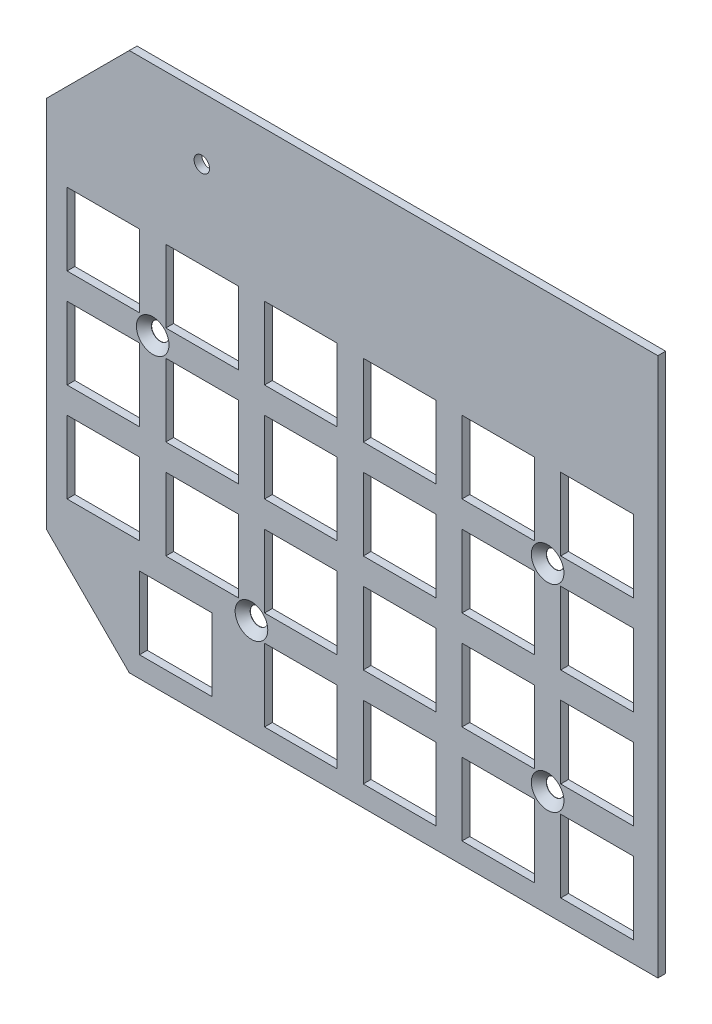
SolidWorks part; units mm, degrees
material "Alliage 1060"
ref_plane "Plan de face" through (0, 0, 0) normal (0, 0, 1) x (1, 0, 0)
ref_plane "Plan de dessus" through (0, 0, 0) normal (0, 1, 0) x (1, 0, 0)
ref_plane "Plan de droite" through (0, 0, 0) normal (1, 0, 0) x (0, 0, -1)
other "Centre de masse"
sketch "Esquisse1" plane through (0, 0, 0) normal (0, 0, 1) x (1, 0, 0)
  line L0 (0, -85) -> (16, -101)
  line L4 (118, 3) -> (118, -101)
  line L5 (16, 3) -> (0, -13)
  line L7 (118, 3) -> (16, 3)
  line L8 (0, -13) -> (0, -85)
  line L9 (16, -101) -> (118, -101)
  dimension "D1" = 104
  dimension "D2" = 118
  dimension "D3" = 16
  dimension "D4" = 16
  dimension "D5" = 16
  dimension "D6" = 16
extrude "Boss.-Extru.1" add sketch "Esquisse1" along normal blind 1.5
sketch "Esquisse2" plane through (0, 0, 1.5) normal (0, 0, 1) x (1, 0, 0)
  line L0 (0, -13) -> (0, -85) construction
  line L1 (4, -25.85) -> (18, -25.85)
  line L2 (4, -25.85) -> (4, -39.85)
  line L3 (4, -39.85) -> (18, -39.85)
  line L4 (18, -25.85) -> (18, -39.85)
  line L5 (11, -39.85) -> (11, -25.85) construction
  line L6 (4, -32.85) -> (18, -32.85) construction
  line L7 (118, 3) -> (16, 3) construction
  line L12 (23.05, -25.85) -> (23.05, -39.85)
  line L13 (23.05, -25.85) -> (37.05, -25.85)
  line L14 (37.05, -25.85) -> (37.05, -39.85)
  line L15 (23.05, -39.85) -> (37.05, -39.85)
  line L16 (42.1, -25.85) -> (42.1, -39.85)
  line L17 (42.1, -25.85) -> (56.1, -25.85)
  line L18 (56.1, -25.85) -> (56.1, -39.85)
  line L19 (42.1, -39.85) -> (56.1, -39.85)
  line L20 (61.15, -25.85) -> (61.15, -39.85)
  line L21 (61.15, -25.85) -> (75.15, -25.85)
  line L22 (75.15, -25.85) -> (75.15, -39.85)
  line L23 (61.15, -39.85) -> (75.15, -39.85)
  line L24 (80.2, -25.85) -> (80.2, -39.85)
  line L25 (80.2, -25.85) -> (94.2, -25.85)
  line L26 (94.2, -25.85) -> (94.2, -39.85)
  line L27 (80.2, -39.85) -> (94.2, -39.85)
  line L28 (99.25, -25.85) -> (99.25, -39.85)
  line L29 (99.25, -25.85) -> (113.25, -25.85)
  line L30 (113.25, -25.85) -> (113.25, -39.85)
  line L31 (99.25, -39.85) -> (113.25, -39.85)
  line L32 (23.05, -44.9) -> (23.05, -58.9)
  line L33 (23.05, -44.9) -> (37.05, -44.9)
  line L34 (37.05, -44.9) -> (37.05, -58.9)
  line L35 (23.05, -58.9) -> (37.05, -58.9)
  line L36 (42.1, -44.9) -> (42.1, -58.9)
  line L37 (42.1, -44.9) -> (56.1, -44.9)
  line L38 (56.1, -44.9) -> (56.1, -58.9)
  line L39 (42.1, -58.9) -> (56.1, -58.9)
  line L40 (61.15, -44.9) -> (61.15, -58.9)
  line L41 (61.15, -44.9) -> (75.15, -44.9)
  line L42 (75.15, -44.9) -> (75.15, -58.9)
  line L43 (61.15, -58.9) -> (75.15, -58.9)
  line L44 (80.2, -44.9) -> (80.2, -58.9)
  line L45 (80.2, -44.9) -> (94.2, -44.9)
  line L46 (94.2, -44.9) -> (94.2, -58.9)
  line L47 (80.2, -58.9) -> (94.2, -58.9)
  line L48 (99.25, -44.9) -> (99.25, -58.9)
  line L49 (99.25, -44.9) -> (113.25, -44.9)
  line L50 (113.25, -44.9) -> (113.25, -58.9)
  line L51 (99.25, -58.9) -> (113.25, -58.9)
  line L52 (23.05, -63.95) -> (23.05, -77.95)
  line L53 (23.05, -63.95) -> (37.05, -63.95)
  line L54 (37.05, -63.95) -> (37.05, -77.95)
  line L55 (23.05, -77.95) -> (37.05, -77.95)
  line L56 (42.1, -63.95) -> (42.1, -77.95)
  line L57 (42.1, -63.95) -> (56.1, -63.95)
  line L58 (56.1, -63.95) -> (56.1, -77.95)
  line L59 (42.1, -77.95) -> (56.1, -77.95)
  line L60 (61.15, -63.95) -> (61.15, -77.95)
  line L61 (61.15, -63.95) -> (75.15, -63.95)
  line L62 (75.15, -63.95) -> (75.15, -77.95)
  line L63 (61.15, -77.95) -> (75.15, -77.95)
  line L64 (80.2, -63.95) -> (80.2, -77.95)
  line L65 (80.2, -63.95) -> (94.2, -63.95)
  line L66 (94.2, -63.95) -> (94.2, -77.95)
  line L67 (80.2, -77.95) -> (94.2, -77.95)
  line L68 (99.25, -63.95) -> (99.25, -77.95)
  line L69 (99.25, -63.95) -> (113.25, -63.95)
  line L70 (113.25, -63.95) -> (113.25, -77.95)
  line L71 (99.25, -77.95) -> (113.25, -77.95)
  line L72 (4, -44.9) -> (4, -58.9)
  line L73 (4, -44.9) -> (18, -44.9)
  line L74 (18, -44.9) -> (18, -58.9)
  line L75 (4, -58.9) -> (18, -58.9)
  line L76 (4, -63.95) -> (4, -77.95)
  line L77 (4, -63.95) -> (18, -63.95)
  line L78 (18, -63.95) -> (18, -77.95)
  line L79 (4, -77.95) -> (18, -77.95)
  line L112 (42.1, -83) -> (42.1, -97)
  line L113 (42.1, -83) -> (56.1, -83)
  line L114 (56.1, -83) -> (56.1, -97)
  line L115 (42.1, -97) -> (56.1, -97)
  line L116 (61.15, -83) -> (61.15, -97)
  line L117 (61.15, -83) -> (75.15, -83)
  line L118 (75.15, -83) -> (75.15, -97)
  line L119 (61.15, -97) -> (75.15, -97)
  line L120 (80.2, -83) -> (80.2, -97)
  line L121 (80.2, -83) -> (94.2, -83)
  line L122 (94.2, -83) -> (94.2, -97)
  line L123 (80.2, -97) -> (94.2, -97)
  line L124 (99.25, -83) -> (99.25, -97)
  line L125 (99.25, -83) -> (113.25, -83)
  line L126 (113.25, -83) -> (113.25, -97)
  line L127 (99.25, -97) -> (113.25, -97)
  line L128 (4, -83) -> (4, -97) [skipped]
  line L129 (4, -83) -> (18, -83) [skipped]
  line L130 (18, -83) -> (18, -97) [skipped]
  line L131 (4, -97) -> (18, -97) [skipped]
  line L132 (23.05, -83) -> (23.05, -97) [skipped]
  line L133 (23.05, -83) -> (37.05, -83) [skipped]
  line L134 (37.05, -83) -> (37.05, -97) [skipped]
  line L135 (23.05, -97) -> (37.05, -97) [skipped]
  line L137 (17.97, -83) -> (31.97, -83)
  line L138 (17.97, -83) -> (17.97, -97)
  line L139 (17.97, -97) -> (31.97, -97)
  line L140 (31.97, -83) -> (31.97, -97)
  line L141 (24.97, -97) -> (24.97, -83) construction
  line L142 (17.97, -90) -> (31.97, -90) construction
  line L143 (16, -101) -> (118, -101) construction
  circle A8 centre (30, -9) radius 1.5
  point P0 (11, -32.85)
  point P19 (24.97, -90)
  dimension "D5" = 4
  dimension "D13" = 5.05
  dimension "D7" = 12
  dimension "D6" = 30
  dimension "D1" = 14
  dimension "D2" = 14
  dimension "D3" = 4
  dimension "D4" = 6
  dimension "D9" = 14
  dimension "D10" = 14
  dimension "D11" = 10.13
  dimension "D12" = 5.05
  dimension "D8" = 4
extrude "Enlèv. mat.-Extru.1" cut sketch "Esquisse2" against normal blind 1.5
sketch "Esquisse9" plane through (0, 0, 1.5) normal (0, 0, 1) x (1, 0, 0)
  line L0 (18, -44.9) -> (23.05, -39.85) construction
  line L1 (94.2, -39.85) -> (99.25, -44.9) construction
  line L2 (94.2, -83) -> (99.25, -77.95) construction
  line L3 (37.05, -77.95) -> (42.1, -83) construction
  point P16 (20.525, -42.375)
  point P17 (39.575, -80.475)
  point P18 (96.725, -42.375)
  point P19 (96.725, -80.475)
hole_wizard "Fraisage pour vis à tête fraisée M31" positions "Esquisse17" profile "Esquisse18" countersink size "M3" standard "Ansi Metric" end condition through all
sketch "Esquisse17" plane through (0, 0, 1.5) normal (0, 0, 1) x (1, 0, 0)
  point P0 (20.525, -42.375)
  point P4 (96.725, -42.375)
  point P7 (96.725, -80.475)
  point P10 (39.575, -80.475)
sketch "Esquisse18" plane through (20.525, -42.375, 1.5) normal (1, 0, 0) x (0, -1, 0)
  line L0 (0, 0) -> (0, 1.5)
  line L1 (0, 1.5) -> (1.7, 1.5)
  line L2 (1.7, 1.5) -> (1.7, 1.45)
  line L3 (1.7, 1.45) -> (3.15, 0)
  line L5 (3.15, 0) -> (0, 0)
  line L6 (-1.7, 1.45) -> (-3.15, 0) construction
  line L11 (0, -6.35) -> (0, 107.95) construction
  dimension "Diamètre du perçage jusqu'au prochain" = 3.4
  dimension "Profondeur du perçage jusqu'au prochain" = 1.5
  dimension "Diamètre du fraisage entrant" = 6.3
  dimension "Angle du fraisage entrant" = 90
